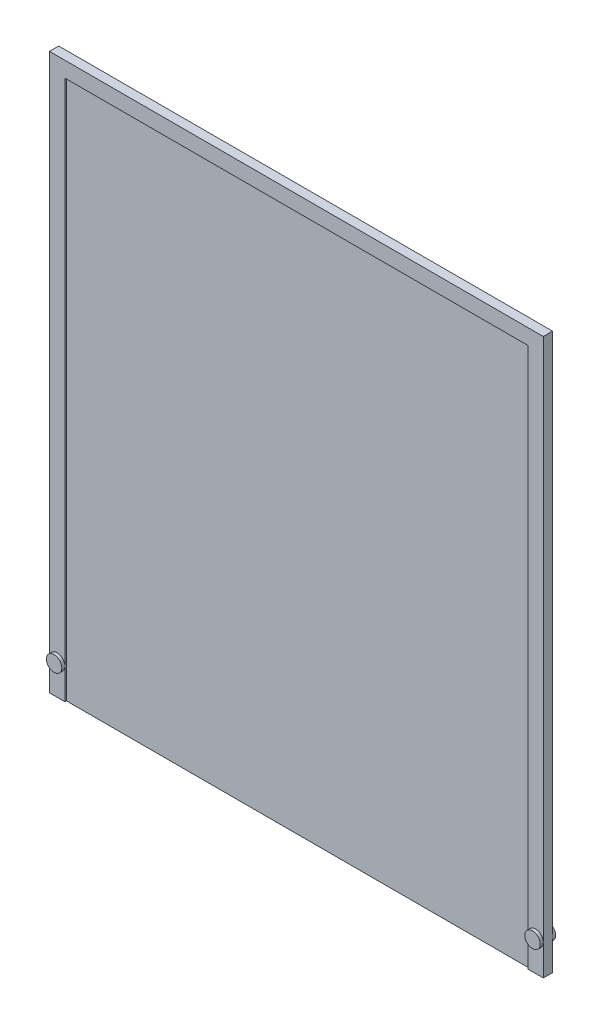
SolidWorks part; units mm, degrees
ref_plane "前视基准面" through (0, 0, 0) normal (0, 0, 1) x (1, 0, 0)
ref_plane "上视基准面" through (0, 0, 0) normal (0, 1, 0) x (1, 0, 0)
ref_plane "右视基准面" through (0, 0, 0) normal (1, 0, 0) x (0, 0, -1)
sketch "草图1" plane through (0, 0, 0) normal (0, 0, 1) x (1, 0, 0)
  line L1 (-80, -90) -> (80, -90)
  line L2 (-80, -90) -> (-80, 90)
  line L3 (-80, 90) -> (80, 90)
  line L4 (80, -90) -> (80, 90)
  line L5 (-80, -90) -> (80, 90) construction
  line L6 (-80, 90) -> (80, -90) construction
  point P0 (0, 0)
  dimension "D1" = 180
  dimension "D2" = 160
extrude "凸台-拉伸1" add sketch "草图1" along normal mid plane 3
sketch "草图2" plane through (0, 0, 1.5) normal (0, 0, 1) x (1, 0, 0)
  line L0 (0, 0) -> (0, 10) construction
  line L2 (-75, -90) -> (-75, 85)
  line L3 (-75, 85) -> (75, 85)
  line L4 (75, -90) -> (75, 85)
  line L5 (0, -90) -> (0, 0) construction
  line L6 (80, 90) -> (-80, 90) construction
  line L8 (-80, -90) -> (80, -90) construction
  line L9 (-75, -90) -> (75, -90)
  point P0 (7.027, 3.6999)
  dimension "D1" = 5
  dimension "D3" = 10
  dimension "D4" = 150
extrude "切除-拉伸1" cut sketch "草图2" against normal blind 0.5
sketch "草图3" plane through (0, 0, 0) normal (0, 0, 1) x (1, 0, 0)
  line L0 (-77.5, -90) -> (-77.5, -80) construction
  line L1 (-80, -90) -> (-75, -90) construction
  line L2 (0, -90) -> (0, -27.5045) construction
  line L3 (-75, -90) -> (75, -90) construction
  circle A0 centre (-77.5, -80) radius 2.5
  circle A1 centre (77.5, -80) radius 2.5
  dimension "D1" = 5
  dimension "D2" = 10
extrude "凸台-拉伸2" add sketch "草图3" along normal mid plane 5
